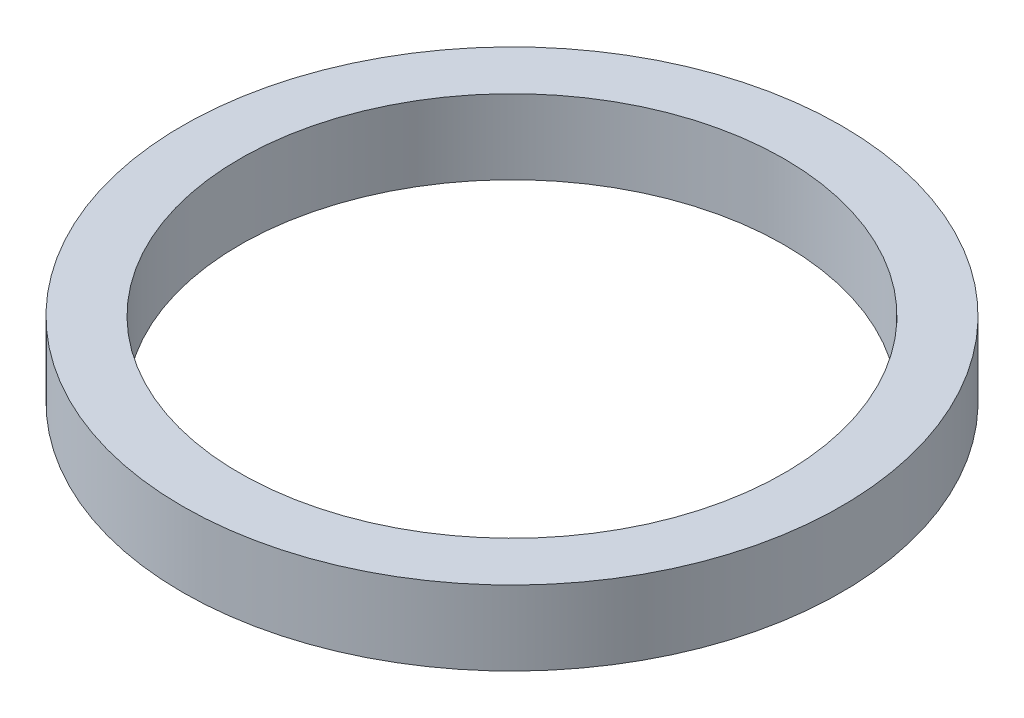
SolidWorks part; units mm, degrees
ref_plane "Front Plane" through (0, 0, 0) normal (0, 0, 1) x (1, 0, 0)
ref_plane "Top Plane" through (0, 0, 0) normal (0, 1, 0) x (1, 0, 0)
ref_plane "Right Plane" through (0, 0, 0) normal (1, 0, 0) x (0, 0, -1)
sketch "Sketch1" plane through (0, 0, 0) normal (0, 1, 0) x (1, 0, 0)
  circle A0 centre (0, 0) radius 57.5
  dimension "FLANGE_OD" = 115
extrude "Boss-Extrude1" add sketch "Sketch1" along normal blind 13
sketch "Sketch2" plane through (0, 0, 0) normal (0, 1, 0) x (1, 0, 0)
  circle A0 centre (0, 0) radius 47.5
  dimension "BORE_D" = 95
extrude "Cut-Extrude1" cut sketch "Sketch2" along normal through all
sketch "Sketch3" plane through (0, 13, 0) normal (0, 1, 0) x (1, 0, 0)
  circle A0 centre (0, 0) radius 25.3705 construction
  circle A1 centre (-25.3705, 0) radius 1.5093
  dimension "BOLT_D" = 3.0185
  dimension "BOLT_PCD" = 50.741
extrude "Cut-Extrude2" cut sketch "Sketch3" against normal blind 8.1385 rebuild error yes
pattern_circular "CirPattern1" count 5 over 360 rebuild error yes
